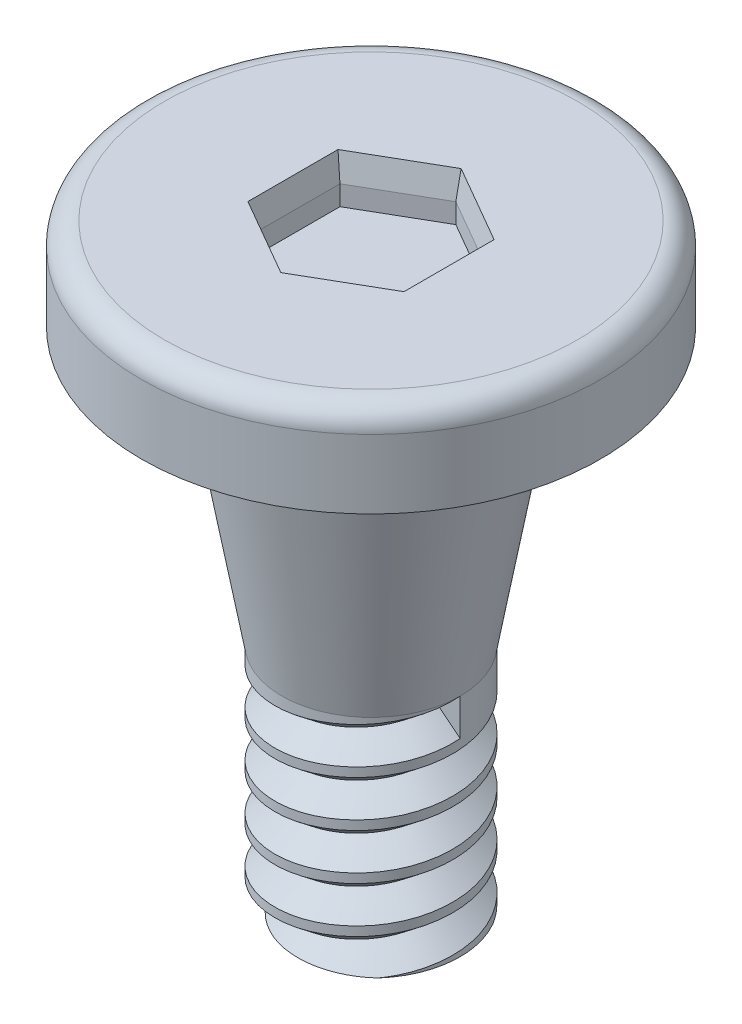
SolidWorks part; units mm, degrees
ref_plane "Plan de face" through (0, 0, 0) normal (0, 0, 1) x (1, 0, 0)
ref_plane "Plan de dessus" through (0, 0, 0) normal (0, 1, 0) x (1, 0, 0)
ref_plane "Plan de droite" through (0, 0, 0) normal (1, 0, 0) x (0, 0, -1)
sketch "Esquisse1" plane through (0, 0, 0) normal (0, 0, 1) x (1, 0, 0)
  line L0 (-3, 0) -> (-1.942, -6)
  line L1 (-3, 0) -> (-5, 0)
  line L2 (0, 0) -> (0, 2)
  line L3 (0, 2) -> (-5, 2)
  line L4 (-5, 0) -> (-5, 2)
  line L5 (-1.942, -6) -> (-1.942, -11)
  line L6 (-1.942, -11) -> (0, -11)
  line L7 (0, -11) -> (0, 0)
  dimension "D1" = 5
  dimension "D2" = 2
  dimension "D3" = 3
  dimension "D4" = 80
  dimension "D5" = 6
  dimension "D6" = 5
revolve "Révolution1" add sketch "Esquisse1" angle 360 about L7
ref_plane "Plan1" through (0, -6, 0) normal (0, 1, 0) x (1, 0, 0)
sketch "Esquisse2" plane through (0, -6, 0) normal (0, 1, 0) x (1, 0, 0)
  circle A0 centre (0, 0) radius 1.95
curve "Hélice/Spirale1" pitch 1 height 5 radius 1.95 centre (0, -6, 0) axis (0, -1, 0) start towards (1, 0, 0)
sketch "Esquisse3" plane through (0, 0, 0) normal (0, 0, 1) x (1, 0, 0)
  line L0 (1.942, -6) -> (1.942, -6.8)
  line L1 (2.1362, -6) -> (-2.1362, -6) construction
  line L2 (1.942, -11) -> (1.942, -6) construction
  line L5 (1.442, -6.4) -> (1.942, -6)
  line L6 (1.942, -6.8) -> (1.442, -6.4)
  dimension "D1" = 0.8
  dimension "D2" = 0.5
sketch "Esquisse4" plane through (0, 0, 0) normal (0, 0, 1) x (1, 0, 0)
  line L0 (0, -10.8604) -> (0, -12.4734) construction
  line L2 (0, -12.0701) -> (3.2929, -12.0701)
  line L3 (0, -12.0701) -> (0, -10.9164)
  line L4 (0, -10.9164) -> (3.2929, -10.9164)
  line L5 (3.2929, -12.0701) -> (3.2929, -10.9164)
revolve "Enlèvement de matière-Révolution1" cut sketch "Esquisse4" angle 360 about L0
sketch "Esquisse5" plane through (0, 2, 0) normal (0, 1, 0) x (1, 0, 0)
  line L1 (0, 1.8475) -> (-1.6, 0.9238)
  line L2 (-1.6, 0.9238) -> (-1.6, -0.9238)
  line L3 (-1.6, -0.9238) -> (0, -1.8475)
  line L4 (0, -1.8475) -> (1.6, -0.9238)
  line L5 (1.6, -0.9238) -> (1.6, 0.9238)
  line L6 (1.6, 0.9238) -> (0, 1.8475)
  circle A0 centre (0, 0) radius 1.6 construction
extrude "Enlèv. mat.-Extru.1" cut sketch "Esquisse5" against normal blind 1
chamfer "Chanfrein1" distance 0.1 angle 80 6 edges at (-1.6, 2, 0) (-0.8, 2, 1.3856) (0.8, 2, 1.3856) (1.6, 2, 0) (0.8, 2, -1.3856) (-0.8, 2, -1.3856) first distance on face at (0, 2, 0)
fillet "Congé1" radius 0.5 1 edges at (0, 2, -5)
sweep "Enlèvement de matière-Balayage1" cut profiles "Esquisse3" path "Hélice/Spirale1"
